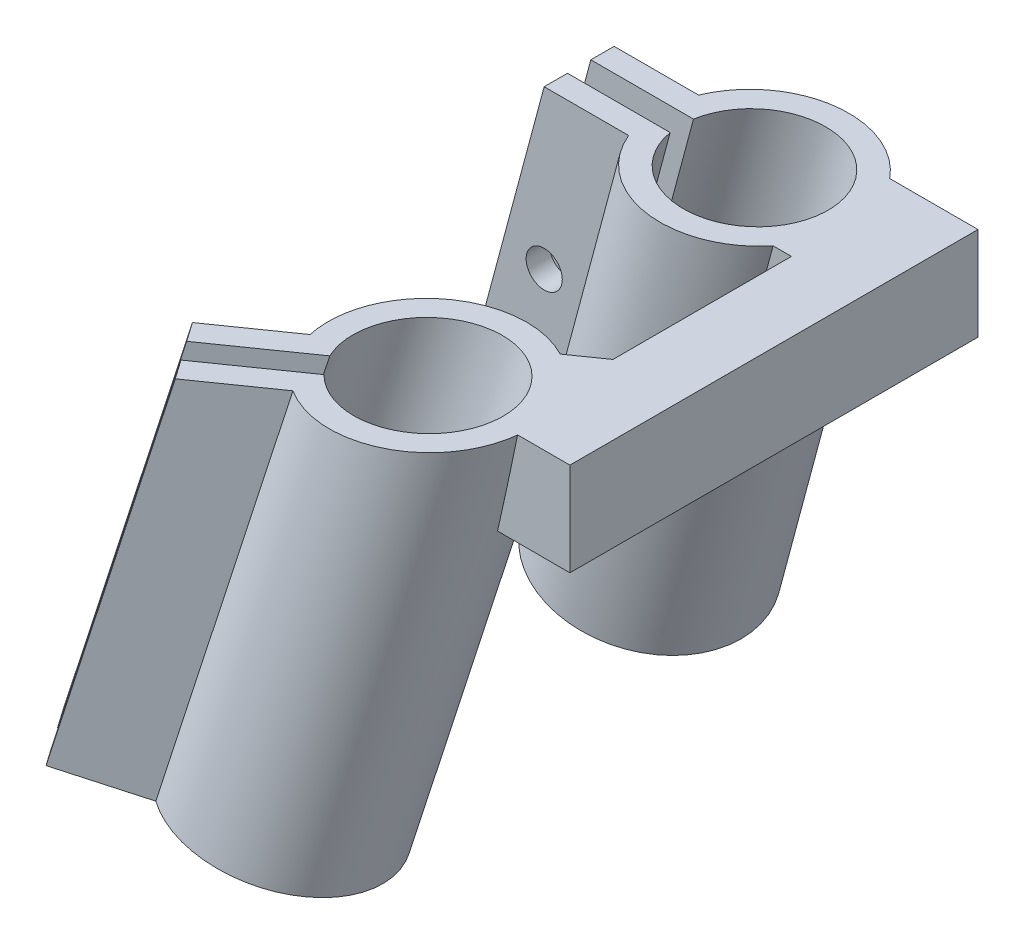
SolidWorks part; units mm, degrees
ref_plane "Front Plane" through (0, 0, 0) normal (0, 0, 1) x (1, 0, 0)
ref_plane "Top Plane" through (0, 0, 0) normal (0, 1, 0) x (1, 0, 0)
ref_plane "Right Plane" through (0, 0, 0) normal (1, 0, 0) x (0, 0, -1)
sketch "Sketch1" plane through (0, 0, 0) normal (0, 1, 0) x (0, 0, -1)
  line L11 (0, 0) -> (35, 0)
  line L17 (35, 0) -> (35, 10)
  line L18 (35, 10) -> (25, 10)
  line L19 (25, 10) -> (25, 6)
  line L20 (25, 6) -> (9.6944, 6)
  line L22 (0, 55) -> (0, -55) construction
  line L29 (0, 0) -> (0, 7.2478)
  line L33 (0, 7.2478) -> (5.9187, 11.3921)
  line L34 (5.9187, 11.3921) -> (9.6944, 6)
  line L36 (0, 7.2478) -> (3.8088, 7.2478) construction
  point P6 (30, 19.2547)
  point P7 (30, 0)
  dimension "D2" = 10
  dimension "D3" = 35
  dimension "D4" = 10
  dimension "D1" = 6
  dimension "D5" = 35
extrude "Boss-Extrude1" add sketch "Sketch1" along normal mid plane 8 contours L19 | L20 L11 | L17 region at (-4.2316, 0, -17.9335)
sketch "Sketch4" plane through (0, 0, -35) normal (0, 0, -1) x (-1, 0, 0)
  line L0 (10, 4) -> (7.8564, 4)
  line L1 (0, 4) -> (10, 4) construction
  line L2 (7.8564, 4) -> (10, -4)
  line L3 (10, -4) -> (10, 4)
  dimension "D1" = 15
extrude "Cut-Extrude2" cut sketch "Sketch4" against normal blind 10
ref_plane "Plane1" through (-1.6699, -6.2321, 0) normal (-0.2588, -0.9659, 0) x (0, 0, 1)
sketch "Sketch2" plane through (2.4798, -7.344, 20) normal (0.2588, 0.9659, 0) x (-0.9659, 0.2588, 0)
  line L0 (25.0375, -49) -> (33.544, -49)
  line L1 (33.544, -49) -> (33.544, -47)
  line L2 (33.544, -47) -> (26.544, -47)
  line L3 (25.0375, -51) -> (33.544, -51)
  line L4 (33.544, -51) -> (33.544, -53)
  line L5 (33.544, -53) -> (26.544, -53)
  line L6 (33.544, -49) -> (33.544, -51) construction
  line L7 (12.9201, -45) -> (12.9201, -55) construction
  line L11 (12.9201, -45) -> (12.9201, -55) construction
  arc A0 (25.0375, -49) -> (25.0375, -51) centre (19.0201, -50) ccw
  arc A2 (26.544, -47) -> (26.544, -53) centre (19.0201, -50) ccw
  point P0 (5, 16.1)
  point P1 (33.544, -50)
  point P2 (5, 16.1)
  point P6 (20.309, 69.9496)
  point P10 (17.8256, 73.1838)
  point P30 (12.9201, -50)
  dimension "D2" = 6.1
  dimension "D1" = 2
  dimension "D3" = 2
  dimension "D4" = 2
  dimension "D5" = 7
extrude "Boss-Extrude2" add sketch "Sketch2" along normal up to surface and the other way blind 28 up to face at (-5.7941, 4, -16.9516)
sketch "Sketch5" plane through (0, 0, -35) normal (0, 0, -1) x (-1, 0, 0)
  circle A0 centre (29.2062, -9.5471) radius 1.55
  dimension "D1" = 3.1
extrude "Cut-Extrude3" cut sketch "Sketch5" against normal through all both and the other way through all
sketch "Sketch7" plane through (-8.9168, -33.278, 0) normal (0.2588, 0.9659, 0) x (-0.9659, 0.2588, 0)
  line L7 (20.7415, -29) -> (29.2479, -29) construction
  line L8 (29.2479, -31) -> (20.7415, -31) construction
  line L9 (20.9441, -29) -> (19.725, -29)
  line L10 (20.9441, -31) -> (19.725, -31)
  arc A3 (20.9388, -28.9672) -> (20.9388, -31.0328) centre (14.724, -30) ccw
  arc A4 (20.9441, -29) -> (20.9441, -31) centre (14.724, -30) ccw
  arc A7 (19.755, -29.1639) -> (19.755, -30.8361) centre (14.724, -30) ccw
  arc A8 (19.725, -29) -> (19.725, -31) centre (14.724, -30) ccw
  point P3 (11.9244, -25)
  point P4 (15.969, -24.3279)
  point P5 (15.969, -25.6721)
  dimension "D1" = 0.2
  dimension "D2" = 1
extrude "Boss-Extrude3" add sketch "Sketch7" along normal blind 0.5
sketch "Sketch8" plane through (-6.5288, 0, -9.3241) normal (-0.5736, 0, -0.8192) x (-0.8192, 0, 0.5736)
  line L0 (5.937, 4) -> (5.937, -4)
  line L1 (5.937, -4) -> (3.7934, 4)
  line L2 (5.937, 4) -> (-0.6455, 4) construction
  line L3 (3.7934, 4) -> (5.937, 4)
  dimension "D1" = 15
extrude "Cut-Extrude4" cut sketch "Sketch8" against normal through all
ref_plane "Plane2" through (-1.1449, -5.2163, 0.8017) normal (0.212, 0.9659, -0.1485) x (-0.5736, 0, -0.8192)
sketch "Sketch9" plane through (-1.1449, -5.2163, 0.8017) normal (0.212, 0.9659, -0.1485) x (-0.5736, 0, -0.8192)
  line L15 (6.7699, 16.8169) -> (6.7699, 25.3234)
  line L17 (6.7699, 25.3234) -> (4.7699, 25.3234)
  line L18 (4.7699, 25.3234) -> (4.7699, 18.3234)
  line L19 (8.7699, 16.8169) -> (8.7699, 25.3234)
  line L20 (8.7699, 25.3234) -> (10.7699, 25.3234)
  line L21 (10.7699, 25.3234) -> (10.7699, 18.3234)
  line L22 (6.7699, 25.3234) -> (8.7699, 25.3234) construction
  line L23 (4.1571, 4.6994) -> (11.3826, 4.6994) construction
  line L24 (4.1571, 4.6994) -> (11.3826, 4.6994) construction
  arc A4 (6.7699, 16.8169) -> (8.7699, 16.8169) centre (7.7699, 10.7994) ccw
  arc A5 (4.7699, 18.3234) -> (10.7699, 18.3234) centre (7.7699, 10.7994) ccw
  circle A7 centre (7.7699, 10.7994) radius 8.1 construction
  circle A8 centre (7.7699, 10.7994) radius 6.1 construction
  point P1 (7.7699, 25.3234)
  point P10 (73.4733, 60.2816)
  point P14 (71.5607, 59.6969)
  point P15 (33.5723, -33.7437)
  point P22 (7.7699, 4.6994)
  point P26 (14.8934, 6.2232)
  point P28 (12.6268, 8.0066)
  dimension "D4" = 2
  dimension "D5" = 7
  dimension "D2" = 12.2
  dimension "D1" = 2
  dimension "D3" = 2
extrude "Boss-Extrude4" add sketch "Sketch9" along normal up to surface and the other way blind 28 up to face at (-14.4765, 4, -23.5527)
sketch "Sketch10" plane through (-7.0813, -32.2622, 4.9584) normal (-0.212, -0.9659, 0.1485) x (0.9767, -0.2148, -0.0028)
  line L3 (-17.7334, 3.7637) -> (-24.7931, 8.5094) construction
  line L6 (-25.9089, 6.8495) -> (-18.8492, 2.1038) construction
  line L9 (-16.4658, 2.9115) -> (-17.9016, 3.8767)
  line L10 (-17.5816, 1.2517) -> (-19.0174, 2.2169)
  arc A2 (-17.484, 1.4824) -> (-16.6426, 2.7341) centre (-13.2974, -0.4234) ccw
  arc A3 (-17.5816, 1.2517) -> (-16.4658, 2.9115) centre (-13.2974, -0.4234) ccw
  arc A5 (-19.0313, 2.1867) -> (-17.8789, 3.9009) centre (-13.2974, -0.4234) ccw
  arc A6 (-19.0174, 2.2169) -> (-17.9016, 3.8767) centre (-13.2974, -0.4234) ccw
  dimension "D1" = 1.5
  dimension "D2" = 0.2
extrude "Boss-Extrude5" add sketch "Sketch10" against normal blind 0.5
